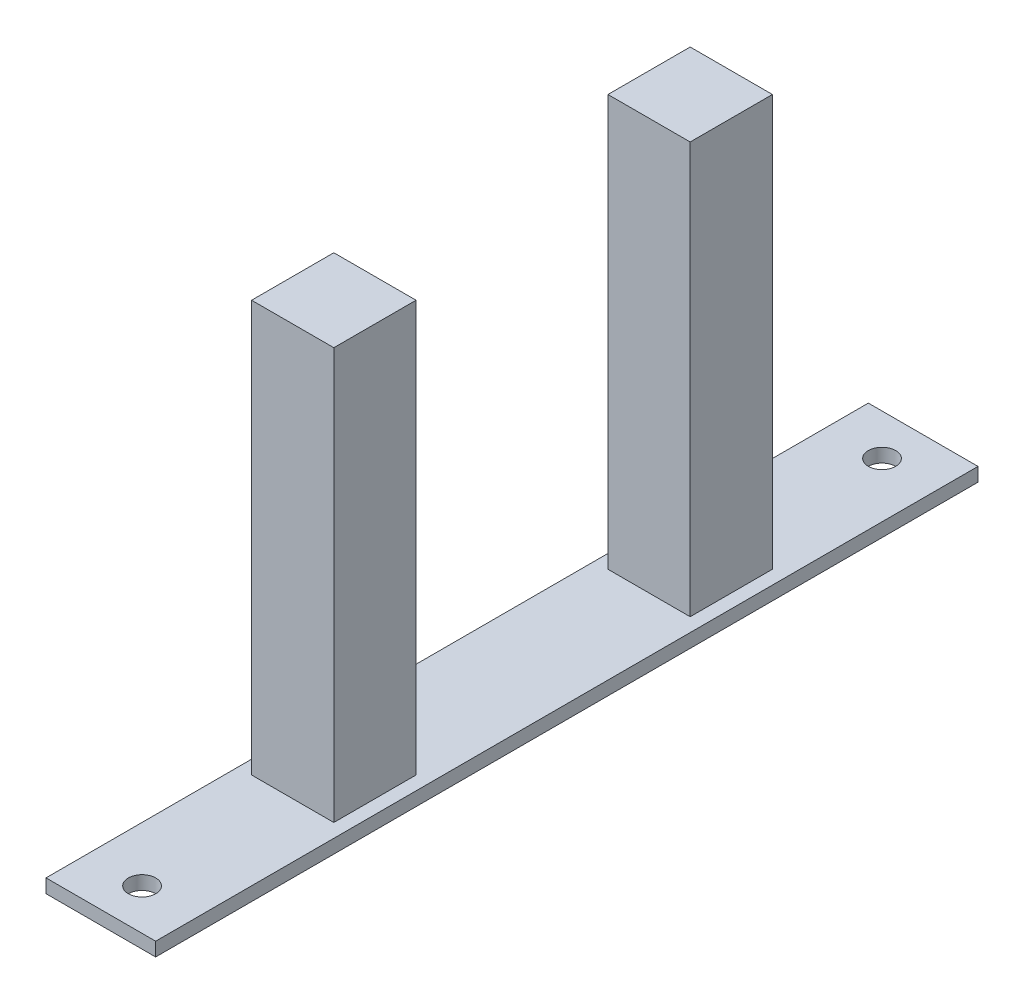
SolidWorks part; units mm, degrees
ref_plane "Front Plane" through (0, 0, 0) normal (0, 0, 1) x (1, 0, 0)
ref_plane "Top Plane" through (0, 0, 0) normal (0, 1, 0) x (1, 0, 0)
ref_plane "Right Plane" through (0, 0, 0) normal (1, 0, 0) x (0, 0, -1)
sketch "Sketch1" plane through (0, 0, 0) normal (0, 1, 0) x (1, 0, 0)
  line L0 (0, -55) -> (0, 55) construction
  line L1 (-20, 150) -> (20, 150)
  line L2 (-20, 150) -> (-20, -150)
  line L3 (-20, -150) -> (20, -150)
  line L4 (20, 150) -> (20, -150)
  line L5 (-20, 150) -> (20, -150) construction
  line L6 (-20, -150) -> (20, 150) construction
  line L7 (-55, 0) -> (55, 0) construction
  point P0 (0, 0)
  dimension "D1" = 40
  dimension "D2" = 300
extrude "Boss-Extrude1" add sketch "Sketch1" along normal blind 5
sketch "Sketch2" plane through (0, 5, 0) normal (0, 1, 0) x (1, 0, 0)
  line L0 (0, -55) -> (0, 55) construction
  line L1 (-15, 80) -> (15, 80)
  line L2 (-15, 80) -> (-15, 50)
  line L3 (-15, 50) -> (15, 50)
  line L4 (15, 80) -> (15, 50)
  line L5 (-15, 80) -> (15, 50) construction
  line L6 (-15, 50) -> (15, 80) construction
  line L7 (20, 150) -> (-20, 150) construction
  line L8 (-20, -150) -> (20, -150) construction
  line L9 (-15, -50) -> (15, -50)
  line L10 (-15, -50) -> (-15, -80)
  line L11 (-15, -80) -> (15, -80)
  line L12 (15, -50) -> (15, -80)
  line L13 (-15, -50) -> (15, -80) construction
  line L14 (-15, -80) -> (15, -50) construction
  point P0 (0, 65)
  point P9 (0, -65)
  point P14 (15, -65)
  dimension "D1" = 30
  dimension "D2" = 30
  dimension "D3" = 70
  dimension "D4" = 30
  dimension "D5" = 30
  dimension "D6" = 70
extrude "Boss-Extrude2" add sketch "Sketch2" along normal blind 150
sketch "Sketch3" plane through (0, 5, 0) normal (0, 1, 0) x (1, 0, 0)
  line L0 (20, 150) -> (-20, 150) construction
  line L1 (-20, -150) -> (20, -150) construction
  circle A0 centre (-0.0227, 135) radius 5
  circle A1 centre (0.0308, -135) radius 7.5
  dimension "D1" = 10
  dimension "D3" = 15
  dimension "D2" = 15
  dimension "D4" = 15
extrude "Cut-Extrude2" cut sketch "Sketch3" against normal up to vertex (5 mm away) contours A0 up to point (-20, 0, -150)
sketch "Sketch6" plane through (0, 5, 0) normal (0, 1, 0) x (1, 0, 0)
  line L0 (-20, -150) -> (20, -150) construction
  circle A0 centre (0.0362, -135) radius 5
  dimension "D1" = 10
  dimension "D2" = 15
extrude "Cut-Extrude3" cut sketch "Sketch6" against normal up to vertex (5 mm away) up to point (-20, 0, 150)
